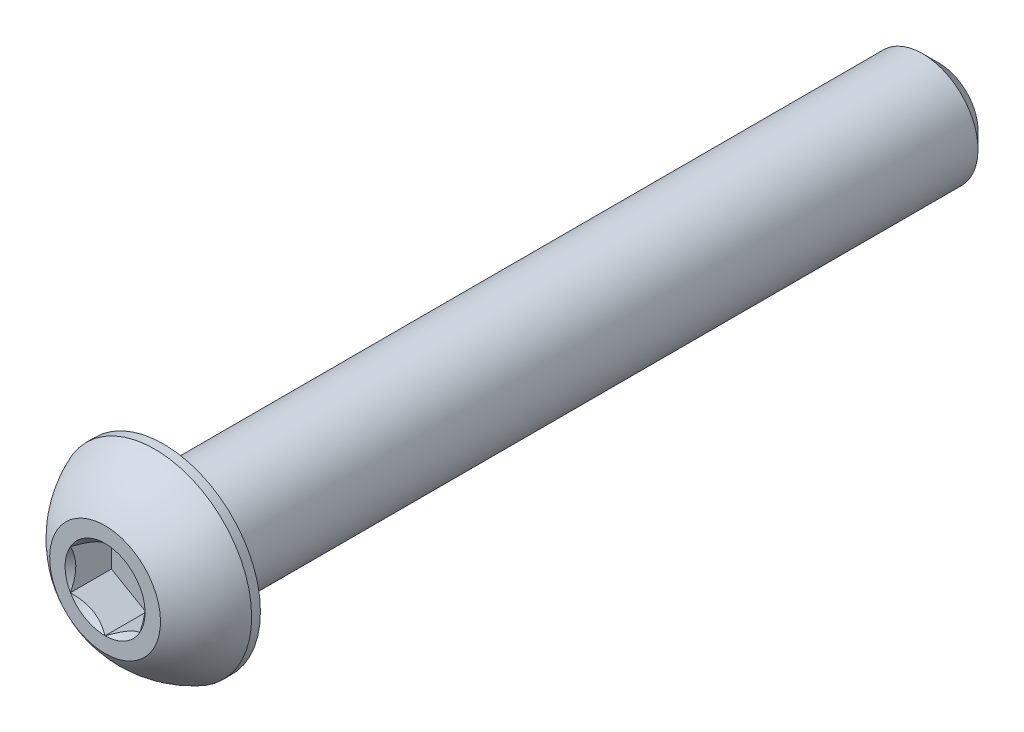
SolidWorks part; units mm, degrees
ref_plane "Front" through (0, 0, 0) normal (0, 0, 1) x (1, 0, 0)
ref_plane "Top" through (0, 0, 0) normal (0, 1, 0) x (1, 0, 0)
ref_plane "Right" through (0, 0, 0) normal (1, 0, 0) x (0, 0, -1)
sketch "Sketch1" plane through (0, 0, 0) normal (1, 0, 0) x (0, 0, -1)
  line L2 (3.3528, 3.175) -> (47.8028, 3.175)
  line L3 (47.8028, 3.175) -> (47.8028, 0)
  line L4 (47.8028, 0) -> (3.3528, 0)
  line L6 (2.8499, 5.5499) -> (3.3528, 5.5499) construction
  line L7 (47.8028, 3.175) -> (47.8028, -3.175) construction
  line L8 (0, 0) -> (3.3528, 0) construction
  line L9 (3.3528, 5.5499) -> (3.3528, -5.5499) construction
  line L11 (3.3528, 3.175) -> (3.3528, 0)
  line L13 (0, 1.9844) -> (0, -1.9844) construction
  line L14 (0, 1.9844) -> (0, 3.175) construction
  arc A3 (0, 3.175) -> (2.8499, 5.5499) centre (5.0603, 0) cw construction
  dimension "D1" = 0.5029
revolve "Revolve1" add sketch "Sketch1" angle 360 mid plane about L4
sketch "Sketch3" plane through (0, 0, -47.8028) normal (0, 0, -1) x (-1, 0, 0)
  circle A0 centre (0, 0) radius 3.175
curve "Helix/Spiral1" pitch 1.27 height 45.72 turns 36
sketch "Sketch2" plane through (0, 0, 0) normal (1, 0, 0) x (0, 0, -1)
  line L0 (47.8028, 3.175) -> (48.9141, 3.175)
  line L1 (48.9141, 3.175) -> (48.4378, 2.3501)
  line L2 (48.4378, 2.3501) -> (48.2791, 2.3501)
  line L3 (48.2791, 2.3501) -> (47.8028, 3.175)
  line L4 (48.0409, 2.7626) -> (48.6759, 2.7626) construction
  dimension "D1" = 60
  dimension "D2" = 0.1588
  dimension "D3" = 0.635
chamfer "Chamfer1" distance 0.9525 angle 45 1 edges at (0, 3.175, -47.8028)
sweep "Cut-Sweep1" [suppressed] cut profiles "Sketch2" path "Helix/Spiral1"
sketch "Sketch7" plane through (0, 0, 0) normal (1, 0, 0) x (0, 0, -1)
  line L6 (2.8499, 5.5499) -> (3.3528, 5.5499) construction
  line L8 (0, 0) -> (3.3528, 0) construction
  line L11 (3.3528, 5.5499) -> (3.3528, -5.5499) construction
  line L12 (2.8499, 5.5499) -> (3.3528, 5.5499)
  line L13 (0, 0) -> (3.3528, 0)
  line L14 (0, 1.9844) -> (0, -1.9844) construction
  line L15 (3.3528, 5.5499) -> (3.3528, 0)
  line L16 (0, 3.175) -> (0, 0)
  arc A2 (2.8499, 5.5499) -> (0, 3.175) centre (5.0603, 0) ccw construction
  arc A3 (2.8499, 5.5499) -> (0, 3.175) centre (5.0603, 0) ccw
revolve "Revolve2" add sketch "Sketch7" angle 360 mid plane about L13
sketch "Sketch5" plane through (0, 0, 0) normal (0, 0, 1) x (1, 0, 0)
  line L1 (1.9844, -1.1457) -> (1.9844, 1.1457)
  line L2 (1.9844, 1.1457) -> (0, 2.2914)
  line L3 (0, 2.2914) -> (-1.9844, 1.1457)
  line L4 (-1.9844, 1.1457) -> (-1.9844, -1.1457)
  line L5 (-1.9844, -1.1457) -> (0, -2.2914)
  line L6 (0, -2.2914) -> (1.9844, -1.1457)
  circle A0 centre (0, 0) radius 1.9844 construction
extrude "Cut-Extrude2" cut sketch "Sketch5" against normal blind 2.347
sketch "Sketch6" plane through (0, 0, 0) normal (0, 0, 1) x (1, 0, 0)
  circle A0 centre (0, 0) radius 2.2914
extrude "Cut-Extrude3" cut sketch "Sketch6" against normal blind 2.347 draft 45
sketch "Sketch9" [suppressed] plane through (0, 0, -5.0546) normal (0, 0, 1) x (1, 0, 0)
  circle A2 centre (0, 0) radius 4.7625
extrude "Boss-Extrude2" [suppressed] add sketch "Sketch9" against normal offset from surface (12.7 mm away) 31.75
sketch "Sketch10" plane through (0, 0, 0) normal (1, 0, 0) x (0, 0, -1)
  line L0 (47.8028, 3.175) -> (47.8028, -3.175) construction
  point P0 (45.8978, -3.175)
  dimension "D1" = 1.905
equation "\"D3@Helix/Spiral1\" = \"Lg@Sketch1\" + \"D4@Helix/Spiral1\""
equation "\"D2@Sketch2\" = \"D4@Helix/Spiral1\" * .125"
equation "\"D3@Sketch2\" = \"D4@Helix/Spiral1\" * .5"
equation "\"D1@Chamfer1\" = \"D4@Helix/Spiral1\" * .75"
equation "\"D1@Cut-Extrude2\" = \"Head Ht@Sketch1\" * .7"
equation "\"D1@Sketch1\" = \"Head Ht@Sketch1\" * .15"
equation "\"D1@Sketch10\" = \"D4@Helix/Spiral1\" * 1.5"
equation "\"D1@Cut-Extrude3\" = \"D1@Cut-Extrude2\""
